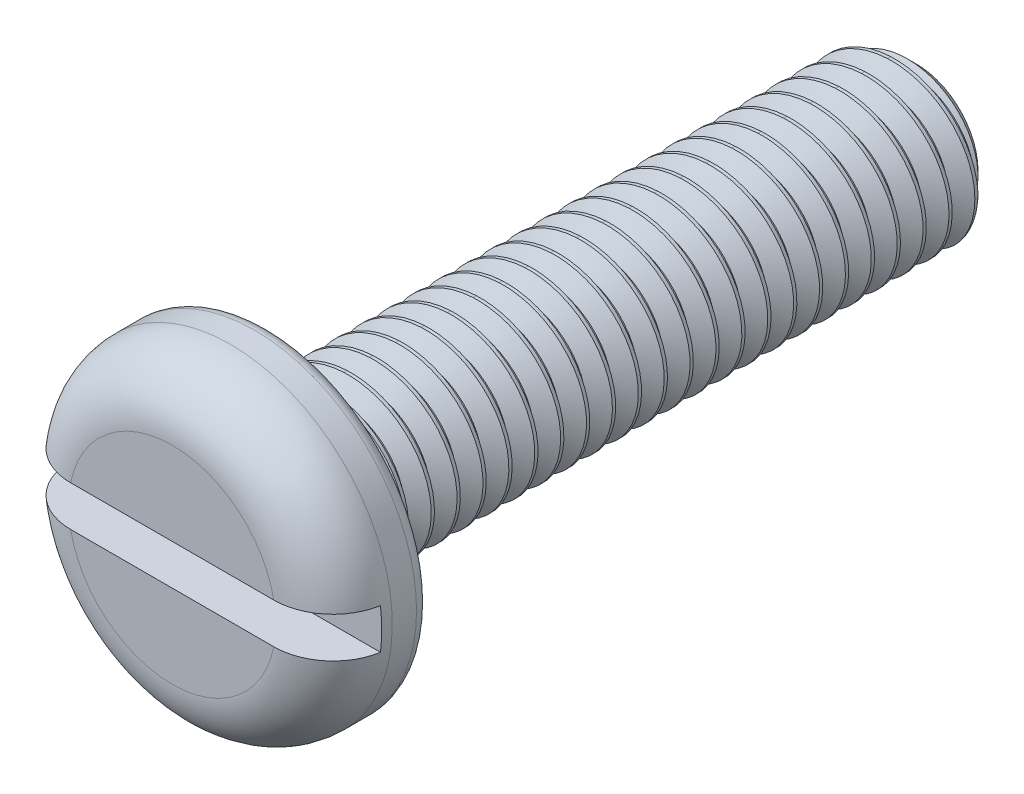
SolidWorks part; units mm, degrees
ref_plane "Front" through (0, 0, 0) normal (0, 0, 1) x (1, 0, 0)
ref_plane "Top" through (0, 0, 0) normal (0, 1, 0) x (1, 0, 0)
ref_plane "Right" through (0, 0, 0) normal (1, 0, 0) x (0, 0, -1)
sketch "Sketch1" plane through (0, 0, 0) normal (0, 0, 1) x (1, 0, 0)
  circle A0 centre (0, 0) radius 5
  dimension "Head Dia" = 10
extrude "Extrude3" add sketch "Sketch1" along normal blind 3
sketch "Sketch11" plane through (0, 0, 0) normal (1, 0, 0) x (0, 0, -1)
  line L0 (0.4414, 0) -> (-3, 0) construction
  line L1 (-3, 3.2) -> (-3.2, 3.2)
  line L2 (-3.2, 3.2) -> (-3.2, 5.2)
  line L3 (0, -5) -> (0, 5) construction
  line L4 (-3.2, 5.2) -> (0, 5.2)
  line L5 (-1.2, 5) -> (0, 5)
  line L6 (-3, 5) -> (-3, -5) construction
  line L7 (0, 5) -> (0, 5.2)
  line L8 (0, 5) -> (-3, 5) construction
  line L9 (-3, 3.2) -> (-3, 0) construction
  arc A0 (-1.2, 5) -> (-3, 3.2) centre (-1.2, 3.2) ccw
  dimension "D2" = 1.8
  dimension "D3" = 3
revolve "Cut-Revolve3" cut sketch "Sketch11" angle 360 about L0
sketch "Sketch4" plane through (0, 0, 0) normal (1, 0, 0) x (0, 0, -1)
  line L0 (0, 0) -> (20, 0)
  line L2 (20, -2.5) -> (0, -2.5) construction
  line L3 (20, 0) -> (20, 2.5)
  line L4 (20, 2.5) -> (0, 2.5)
  line L6 (0, 2.5) -> (0, 0)
  line L7 (20, 0) -> (22.54, 0) construction
  dimension "Screw Dia" = 5
  dimension "D1" = 2.54
  dimension "Screw Length" = 20
revolve "Revolve1" add sketch "Sketch4" angle 360 about L7
chamfer "Chamfer1" distance 0.6 angle 45 1 edges at (2.5, 0, -20)
sketch "Sketch13" plane through (0, 0, 0) normal (1, 0, 0) x (0, 0, -1)
  line L0 (20, 2.5) -> (20.3, 1.9804)
  line L1 (20.3, 1.9804) -> (20.4, 1.9804)
  line L2 (20.4, 1.9804) -> (20.7, 2.5)
  line L3 (20.7, 2.5) -> (20, 2.5)
  line L4 (20.15, 2.2402) -> (20.55, 2.2402) construction
  dimension "D2" = 0.4
  dimension "D3" = 60
sketch "Sketch14" plane through (0, 0, -20) normal (0, 0, -1) x (-1, 0, 0)
  circle A1 centre (0, 0) radius 1.9
  circle A2 centre (0, 0) radius 1.9
  dimension "D1" = 0
curve "Helix/Spiral1" pitch 0.8 height 20.8 turns 26
sweep "Cut-Sweep1" cut profiles "Sketch13" path "Helix/Spiral1"
sketch "Sketch12" plane through (0, 0, 3) normal (0, 0, 1) x (1, 0, 0)
  line L0 (5, -0.625) -> (5, 0.625)
  line L1 (5, 0) -> (-5, 0) construction
  line L2 (5, 0.625) -> (-5, 0.625)
  line L3 (-5, 0.625) -> (-5, -0.625)
  line L8 (-5, -0.625) -> (5, -0.625)
  circle A0 centre (0, 0) radius 5 construction
  dimension "Phillips Width" = 1.25
extrude "Cut-Extrude1" cut sketch "Sketch12" against normal blind 1.5
fillet "Fillet1" radius 0.45 1 edges at (5, 0, 0)
split line "Split Line1"
sketch "Sketch16" plane through (0, 0, 0) normal (1, 0, 0) x (0, 0, -1)
  point P0 (18, -2.5)
sketch "Sketch17" plane through (0, 0, -20) normal (0, 0, -1) x (-1, 0, 0)
  circle A0 centre (0, 0) radius 2.5
  point P3 (0, 2.5)
  point P5 (0, -2.5)
equation "\"D2@Sketch11\"=\"Head Ht@Extrude3\"*.6"
equation "\"D1@Cut-Extrude1\"=\"Head Ht@Extrude3\"*.5"
equation "\"Phillips Width@Sketch12\"=\"Head Dia@Sketch1\"/8"
equation "\"D2@Sketch13\" = \"D4@Helix/Spiral1\" * .5"
equation "\"D1@Sketch13\" = \"D4@Helix/Spiral1\" * .125"
equation "\"D1@Chamfer1\" = \"D4@Helix/Spiral1\" * .75"
equation "\"D3@Helix/Spiral1\" = \"Screw Length@Sketch4\" + \"D4@Helix/Spiral1\""
equation "\"D1@Fillet1\" = \"Head Ht@Extrude3\" * .15"
